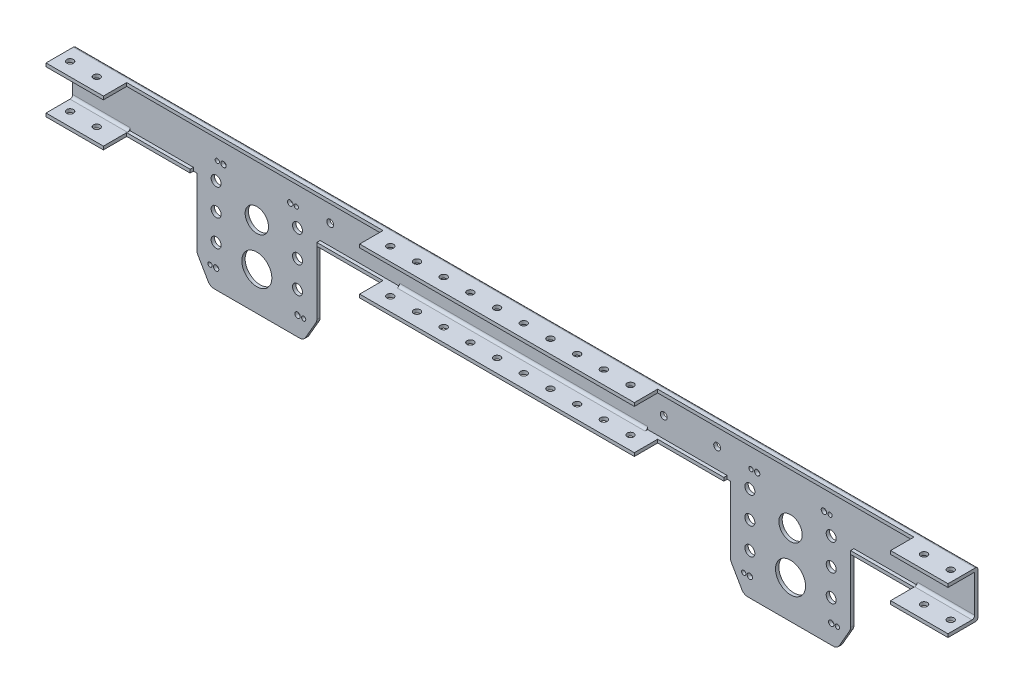
SolidWorks part; units mm, degrees
ref_plane "Front Plane" through (0, 0, 0) normal (0, 0, 1) x (1, 0, 0)
ref_plane "Top Plane" through (0, 0, 0) normal (0, 1, 0) x (1, 0, 0)
ref_plane "Right Plane" through (0, 0, 0) normal (1, 0, 0) x (0, 0, -1)
sketch "Sketch1" plane through (0, 0, 0) normal (0, 0, 1) x (1, 0, 0)
  line L0 (50.8, 0) -> (50.8, 25.4)
  line L1 (-50.8, 0) -> (-50.8, 76.2)
  line L2 (57.15, 31.75) -> (438.15, 31.75)
  line L3 (444.5, 25.4) -> (444.5, 0)
  line L4 (546.1, 0) -> (546.1, 76.2)
  line L5 (-50.8, 76.2) -> (546.1, 76.2)
  arc A0 (-50.8, 0) -> (50.8, 0) centre (0, 0) ccw
  arc A1 (50.8, 25.4) -> (57.15, 31.75) centre (57.15, 25.4) cw
  arc A2 (438.15, 31.75) -> (444.5, 25.4) centre (438.15, 25.4) cw
  arc A3 (444.5, 0) -> (546.1, 0) centre (495.3, 0) ccw
  circle A4 centre (0, 0) radius 6.35
  circle A5 centre (495.3, 0) radius 6.35
  dimension "D1" = 101.6
  dimension "D2" = 6.35
  dimension "D4" = 6.35
  dimension "D6" = 76.2
  dimension "D3" = 381
  dimension "D5" = 25.4
  dimension "D7" = 76.2
extrude "Boss-Extrude1" add sketch "Sketch1" along normal blind 3.175
sketch "Sketch2" plane through (0, 0, 3.175) normal (0, 0, 1) x (1, 0, 0)
  line L0 (-50.8, 76.2) -> (-50.8, 73.025)
  line L1 (-50.8, 76.2) -> (-50.8, 0) construction
  line L2 (546.1, 76.2) -> (-50.8, 76.2)
  line L3 (-50.8, 73.025) -> (546.1, 73.025)
  line L4 (546.1, 0) -> (546.1, 76.2) construction
  line L5 (546.1, 73.025) -> (546.1, 76.2)
  dimension "D1" = 3.175
extrude "Boss-Extrude2" add sketch "Sketch2" along normal blind 25.4
fillet "Fillet1" radius 2.54 2 edges at (247.65, 76.2, 0)
sketch "Sketch3" plane through (0, 76.2, 0) normal (0, 1, 0) x (1, 0, 0)
  line L0 (546.1, -28.575) -> (546.1, -2.54)
  circle A0 centre (527.05, -15.5575) radius 3.2639
  circle A1 centre (501.65, -15.5575) radius 3.2639
  circle A2 centre (476.25, -15.5575) radius 3.2639
  circle A3 centre (450.85, -15.5575) radius 3.2639
  circle A4 centre (425.45, -15.5575) radius 3.2639
  circle A5 centre (400.05, -15.5575) radius 3.2639
  circle A6 centre (374.65, -15.5575) radius 3.2639
  circle A7 centre (349.25, -15.5575) radius 3.2639
  circle A8 centre (323.85, -15.5575) radius 3.2639
  circle A9 centre (298.45, -15.5575) radius 3.2639
  circle A10 centre (273.05, -15.5575) radius 3.2639
  circle A11 centre (247.65, -15.5575) radius 3.2639
  circle A12 centre (222.25, -15.5575) radius 3.2639
  circle A13 centre (196.85, -15.5575) radius 3.2639
  circle A14 centre (171.45, -15.5575) radius 3.2639
  circle A15 centre (146.05, -15.5575) radius 3.2639
  circle A16 centre (120.65, -15.5575) radius 3.2639
  circle A17 centre (95.25, -15.5575) radius 3.2639
  circle A18 centre (69.85, -15.5575) radius 3.2639
  circle A19 centre (44.45, -15.5575) radius 3.2639
  circle A20 centre (19.05, -15.5575) radius 3.2639
  circle A21 centre (-6.35, -15.5575) radius 3.2639
  circle A22 centre (-31.75, -15.5575) radius 3.2639
  dimension "D1" = 19.05
  dimension "D2" = 23
extrude "Cut-Extrude1" cut sketch "Sketch3" against normal blind 25.4 contours A0 | A1 | A2 | A3 | A22 | A21 | A20 | A19 | A18 | A17 | A16 | A15 | A14 | A13 | A12 | A11 | A10 | A9 | A8 | A7 | A6 | A5 | A4 region at (527.05, 76.2, 15.5575) region at (501.65, 76.2, 15.5575) region at (476.25, 76.2, 15.5575) region at (450.85, 76.2, 15.5575) region at (425.45, 76.2, 15.5575) region at (400.05, 76.2, 15.5575) region at (374.65, 76.2, 15.5575) region at (349.25, 76.2, 15.5575) region at (323.85, 76.2, 15.5575) region at (298.45, 76.2, 15.5575) region at (273.05, 76.2, 15.5575) region at (247.65, 76.2, 15.5575) region at (222.25, 76.2, 15.5575) region at (196.85, 76.2, 15.5575) region at (171.45, 76.2, 15.5575) region at (146.05, 76.2, 15.5575) region at (120.65, 76.2, 15.5575) region at (95.25, 76.2, 15.5575) region at (69.85, 76.2, 15.5575) region at (44.45, 76.2, 15.5575) region at (19.05, 76.2, 15.5575) region at (-6.35, 76.2, 15.5575) region at (-31.75, 76.2, 15.5575)
sketch "Sketch5" plane through (0, 0, 0) normal (0, 0, -1) x (-1, 0, 0)
  line L0 (-444.5, 25.4) -> (-444.5, 0) construction
  circle A0 centre (-425.45, 53.975) radius 3.2639
  circle A1 centre (-374.65, 53.975) radius 3.2639
  circle A2 centre (-323.85, 53.975) radius 3.2639
  circle A3 centre (-273.05, 53.975) radius 3.2639
  circle A4 centre (-222.25, 53.975) radius 3.2639
  circle A5 centre (-171.45, 53.975) radius 3.2639
  circle A6 centre (-120.65, 53.975) radius 3.2639
  circle A7 centre (-69.85, 53.975) radius 3.2639
  dimension "D1" = 6.5278
  dimension "D2" = 19.05
  dimension "D3" = 8
extrude "Cut-Extrude2" cut sketch "Sketch5" against normal blind 25.4
sketch "Sketch6" plane through (0, 0, 3.175) normal (0, 0, 1) x (1, 0, 0)
  line L1 (-50.8, 76.2) -> (-82.55, 76.2)
  line L2 (-50.8, 76.2) -> (-50.8, 31.75)
  line L3 (-50.8, 31.75) -> (-82.55, 31.75)
  line L4 (-82.55, 76.2) -> (-82.55, 31.75)
  line L5 (546.1, 76.2) -> (577.85, 76.2)
  line L6 (546.1, 76.2) -> (546.1, 31.75)
  line L7 (546.1, 31.75) -> (577.85, 31.75)
  line L8 (577.85, 76.2) -> (577.85, 31.75)
  dimension "D1" = 31.75
  dimension "D2" = 31.75
extrude "Boss-Extrude3" add sketch "Sketch6" against normal blind 3.175
sketch "Sketch7" plane through (0, 0, 3.175) normal (0, 0, 1) x (1, 0, 0)
  line L1 (57.15, 31.75) -> (438.15, 31.75) construction
  line L2 (-50.8, 73.025) -> (-82.55, 73.025)
  line L3 (-50.8, 73.025) -> (-50.8, 76.2)
  line L4 (-50.8, 76.2) -> (-82.55, 76.2)
  line L5 (-82.55, 31.75) -> (-50.8, 31.75)
  line L6 (-82.55, 31.75) -> (-82.55, 34.925)
  line L7 (-82.55, 34.925) -> (-50.8, 34.925)
  line L8 (-50.8, 31.75) -> (-50.8, 34.925)
  line L9 (577.85, 31.75) -> (577.85, 76.2) construction
  line L10 (546.1, 76.2) -> (577.85, 76.2)
  line L11 (546.1, 76.2) -> (546.1, 73.025)
  line L12 (546.1, 73.025) -> (577.85, 73.025)
  line L13 (577.85, 76.2) -> (577.85, 73.025)
  line L14 (-82.55, 73.025) -> (-82.55, 76.2)
  line L15 (577.85, 31.75) -> (546.1, 31.75)
  line L16 (577.85, 31.75) -> (577.85, 34.925)
  line L17 (577.85, 34.925) -> (546.1, 34.925)
  line L18 (546.1, 31.75) -> (546.1, 34.925)
  line L19 (57.15, 31.75) -> (438.15, 31.75)
  line L20 (57.15, 31.75) -> (57.15, 34.925)
  line L21 (57.15, 34.925) -> (438.15, 34.925)
  line L22 (438.15, 31.75) -> (438.15, 34.925)
  arc A0 (57.15, 31.75) -> (50.8, 25.4) centre (57.15, 25.4) ccw construction
  dimension "D1" = 3.175
  dimension "D2" = 3.175
  dimension "D3" = 3.175
extrude "Boss-Extrude4" add sketch "Sketch7" along normal blind 25.4
fillet "Fillet2" radius 2.54 16 edges at (-50.8, 15.875, 0) (0, -50.8, 0) (50.8, 12.7, 0) (52.6599, 29.8901, 0) (546.1, 15.875, 0) (495.3, -50.8, 0) (444.5, 12.7, 0) (442.6401, 29.8901, 0) (-66.675, 34.925, 3.175) (-66.675, 31.75, 0) (247.65, 31.75, 0) (247.65, 34.925, 3.175) (561.975, 34.925, 3.175) (561.975, 31.75, 0) (561.975, 76.2, 0) (-66.675, 76.2, 0)
sketch "Sketch8" plane through (0, 76.2, 0) normal (0, 1, 0) x (1, 0, 0)
  circle A0 centre (-31.75, -15.5575) radius 3.2639 construction
  circle A1 centre (-31.75, -15.5575) radius 3.2639
  circle A2 centre (-57.15, -15.5575) radius 3.2639
  circle A3 centre (-31.75, -15.5575) radius 3.2639
  circle A4 centre (-6.35, -15.5575) radius 3.2639
  circle A5 centre (19.05, -15.5575) radius 3.2639
  circle A6 centre (44.45, -15.5575) radius 3.2639
  circle A7 centre (69.85, -15.5575) radius 3.2639
  circle A8 centre (95.25, -15.5575) radius 3.2639
  circle A9 centre (120.65, -15.5575) radius 3.2639
  circle A10 centre (146.05, -15.5575) radius 3.2639
  circle A11 centre (171.45, -15.5575) radius 3.2639
  circle A12 centre (196.85, -15.5575) radius 3.2639
  circle A13 centre (222.25, -15.5575) radius 3.2639
  circle A14 centre (247.65, -15.5575) radius 3.2639
  circle A15 centre (273.05, -15.5575) radius 3.2639
  circle A16 centre (298.45, -15.5575) radius 3.2639
  circle A17 centre (323.85, -15.5575) radius 3.2639
  circle A18 centre (349.25, -15.5575) radius 3.2639
  circle A19 centre (374.65, -15.5575) radius 3.2639
  circle A20 centre (400.05, -15.5575) radius 3.2639
  circle A21 centre (425.45, -15.5575) radius 3.2639
  circle A22 centre (450.85, -15.5575) radius 3.2639
  circle A23 centre (476.25, -15.5575) radius 3.2639
  circle A24 centre (501.65, -15.5575) radius 3.2639
  circle A25 centre (527.05, -15.5575) radius 3.2639
  circle A26 centre (-6.35, -15.5575) radius 3.2639
  circle A27 centre (19.05, -15.5575) radius 3.2639
  circle A28 centre (44.45, -15.5575) radius 3.2639
  circle A29 centre (69.85, -15.5575) radius 3.2639
  circle A30 centre (95.25, -15.5575) radius 3.2639
  circle A31 centre (120.65, -15.5575) radius 3.2639
  circle A32 centre (146.05, -15.5575) radius 3.2639
  circle A33 centre (171.45, -15.5575) radius 3.2639
  circle A34 centre (196.85, -15.5575) radius 3.2639
  circle A35 centre (222.25, -15.5575) radius 3.2639
  circle A36 centre (247.65, -15.5575) radius 3.2639
  circle A37 centre (273.05, -15.5575) radius 3.2639
  circle A38 centre (298.45, -15.5575) radius 3.2639
  circle A39 centre (323.85, -15.5575) radius 3.2639
  circle A40 centre (349.25, -15.5575) radius 3.2639
  circle A41 centre (374.65, -15.5575) radius 3.2639
  circle A42 centre (400.05, -15.5575) radius 3.2639
  circle A43 centre (425.45, -15.5575) radius 3.2639
  circle A44 centre (450.85, -15.5575) radius 3.2639
  circle A45 centre (476.25, -15.5575) radius 3.2639
  circle A46 centre (501.65, -15.5575) radius 3.2639
  circle A47 centre (527.05, -15.5575) radius 3.2639
  circle A48 centre (552.45, -15.5575) radius 3.2639
  circle M1 centre (425.45, -15.5575) radius 3.2639
  circle M2 centre (400.05, -15.5575) radius 3.2639
  circle M3 centre (374.65, -15.5575) radius 3.2639
  circle M4 centre (349.25, -15.5575) radius 3.2639
  circle M5 centre (323.85, -15.5575) radius 3.2639
  circle M6 centre (298.45, -15.5575) radius 3.2639
  circle M7 centre (273.05, -15.5575) radius 3.2639
  circle M8 centre (247.65, -15.5575) radius 3.2639
  circle M9 centre (222.25, -15.5575) radius 3.2639
  circle M10 centre (196.85, -15.5575) radius 3.2639
  circle M11 centre (171.45, -15.5575) radius 3.2639
  circle M12 centre (146.05, -15.5575) radius 3.2639
  circle M13 centre (120.65, -15.5575) radius 3.2639
  circle M14 centre (95.25, -15.5575) radius 3.2639
  circle M15 centre (69.85, -15.5575) radius 3.2639
  circle M16 centre (44.45, -15.5575) radius 3.2639
  circle M17 centre (19.05, -15.5575) radius 3.2639
  circle M18 centre (-6.35, -15.5575) radius 3.2639
  circle M19 centre (-31.75, -15.5575) radius 3.2639
  circle M20 centre (450.85, -15.5575) radius 3.2639
  circle M21 centre (476.25, -15.5575) radius 3.2639
  circle M22 centre (501.65, -15.5575) radius 3.2639
  circle M23 centre (527.05, -15.5575) radius 3.2639
  dimension "D1" = 2
  dimension "D2" = 24
extrude "Cut-Extrude3" cut sketch "Sketch8" against normal blind 177.8 contours A2 | M19 | M18 | M17 | M16 | M15 | M14 | M13 | M12 | M11 | M10 | M9 | M8 | M7 | M6 | M5 | M4 | M3 | M2 | M1 | M20 | M21 | A48 | M23 | M22 region at (-31.75, 76.2, 15.5575) region at (-57.15, 76.2, 15.5575) region at (-6.35, 76.2, 15.5575) region at (19.05, 76.2, 15.5575) region at (44.45, 76.2, 15.5575) region at (69.85, 76.2, 15.5575) region at (95.25, 76.2, 15.5575) region at (120.65, 76.2, 15.5575) region at (146.05, 76.2, 15.5575) region at (171.45, 76.2, 15.5575) region at (196.85, 76.2, 15.5575) region at (222.25, 76.2, 15.5575) region at (247.65, 76.2, 15.5575) region at (273.05, 76.2, 15.5575) region at (298.45, 76.2, 15.5575) region at (323.85, 76.2, 15.5575) region at (349.25, 76.2, 15.5575) region at (374.65, 76.2, 15.5575) region at (400.05, 76.2, 15.5575) region at (425.45, 76.2, 15.5575) region at (450.85, 76.2, 15.5575) region at (476.25, 76.2, 15.5575) region at (501.65, 76.2, 15.5575) region at (527.05, 76.2, 15.5575) region at (552.45, 76.2, 15.5575)
sketch "Sketch9" plane through (0, 76.2, 0) normal (0, 1, 0) x (1, 0, 0)
  line L0 (-82.55, -28.575) -> (298.45, -28.575)
  line L1 (577.85, -28.575) -> (-82.55, -28.575) construction
  line L3 (298.45, -28.575) -> (746.3929, -28.575)
  line L4 (298.45, -28.575) -> (298.45, 89.0041)
  line L5 (298.45, 89.0041) -> (746.3929, 89.0041)
  line L6 (746.3929, -28.575) -> (746.3929, 89.0041)
  circle M1 centre (552.45, -15.5575) radius 3.2639
  circle M3 centre (425.45, -15.5575) radius 3.2639
  circle M4 centre (400.05, -15.5575) radius 3.2639
  circle M5 centre (374.65, -15.5575) radius 3.2639
  circle M6 centre (349.25, -15.5575) radius 3.2639
  circle M7 centre (323.85, -15.5575) radius 3.2639
  circle M8 centre (298.45, -15.5575) radius 3.2639
  circle M22 centre (450.85, -15.5575) radius 3.2639
  circle M23 centre (476.25, -15.5575) radius 3.2639
  circle M24 centre (501.65, -15.5575) radius 3.2639
  circle M25 centre (527.05, -15.5575) radius 3.2639
  line M26 (577.85, -28.575) -> (577.85, -2.54)
  line M27 (577.85, -2.54) -> (546.1, -2.54)
  line M28 (546.1, -2.54) -> (-50.8, -2.54)
  line M31 (-82.55, -28.575) -> (577.85, -28.575)
extrude "Cut-Extrude5" cut sketch "Sketch9" against normal blind 432.308 contours L4 M31 M26 M27 M28 M8 M4 M6 M22 M24 M25 M23 M7 M5 M3 M1 | L3 L6 L5 L4 M28 M27 M26 region at (438.4843, 76.2, 15.5575) region at (535.9254, 76.2, -37.5492)
mirror "Mirror4" about plane through (298.45, -356.108, 0) normal (1, 0, 0) of bodies 110
sketch "Sketch10" plane through (-82.55, 0, 0) normal (-1, 0, 0) x (0, 0, 1)
  line L8 (0, 73.66) -> (0, 34.29)
  line L9 (2.54, 31.75) -> (28.575, 31.75)
  line L10 (28.575, 31.75) -> (28.575, 34.925)
  line L11 (28.575, 34.925) -> (5.715, 34.925)
  line L12 (3.175, 37.465) -> (3.175, 73.025)
  line L13 (3.175, 73.025) -> (28.575, 73.025)
  line L14 (28.575, 73.025) -> (28.575, 76.2)
  line L15 (28.575, 76.2) -> (2.54, 76.2)
  line L16 (0, 73.66) -> (0, 34.29)
  line L17 (2.54, 31.75) -> (28.575, 31.75)
  line L18 (28.575, 31.75) -> (28.575, 34.925)
  line L19 (28.575, 34.925) -> (5.715, 34.925)
  line L20 (3.175, 37.465) -> (3.175, 73.025)
  line L21 (3.175, 73.025) -> (28.575, 73.025)
  line L22 (28.575, 73.025) -> (28.575, 76.2)
  line L23 (28.575, 76.2) -> (2.54, 76.2)
  arc A3 (0, 34.29) -> (2.54, 31.75) centre (2.54, 34.29) ccw
  arc A4 (3.175, 37.465) -> (5.715, 34.925) centre (5.715, 37.465) ccw
  arc A5 (2.54, 76.2) -> (0, 73.66) centre (2.54, 73.66) ccw
  arc A6 (0, 34.29) -> (2.54, 31.75) centre (2.54, 34.29) ccw
  arc A7 (3.175, 37.465) -> (5.715, 34.925) centre (5.715, 37.465) ccw
  arc A8 (2.54, 76.2) -> (0, 73.66) centre (2.54, 73.66) ccw
  dimension "D1" = 0
extrude "Boss-Extrude6" add sketch "Sketch10" along normal blind 66.675
sketch "Sketch11" plane through (679.45, 0, 0) normal (1, 0, 0) x (0, 0, -1)
  line L8 (0, 34.29) -> (0, 73.66)
  line L9 (-2.54, 76.2) -> (-28.575, 76.2)
  line L10 (-28.575, 76.2) -> (-28.575, 73.025)
  line L11 (-28.575, 73.025) -> (-3.175, 73.025)
  line L12 (-3.175, 73.025) -> (-3.175, 37.465)
  line L13 (-5.715, 34.925) -> (-28.575, 34.925)
  line L14 (-28.575, 34.925) -> (-28.575, 31.75)
  line L15 (-28.575, 31.75) -> (-2.54, 31.75)
  line L16 (0, 34.29) -> (0, 73.66)
  line L17 (-2.54, 76.2) -> (-28.575, 76.2)
  line L18 (-28.575, 76.2) -> (-28.575, 73.025)
  line L19 (-28.575, 73.025) -> (-3.175, 73.025)
  line L20 (-3.175, 73.025) -> (-3.175, 37.465)
  line L21 (-5.715, 34.925) -> (-28.575, 34.925)
  line L22 (-28.575, 34.925) -> (-28.575, 31.75)
  line L23 (-28.575, 31.75) -> (-2.54, 31.75)
  arc A3 (0, 73.66) -> (-2.54, 76.2) centre (-2.54, 73.66) ccw
  arc A4 (-5.715, 34.925) -> (-3.175, 37.465) centre (-5.715, 37.465) ccw
  arc A5 (-2.54, 31.75) -> (0, 34.29) centre (-2.54, 34.29) ccw
  arc A6 (0, 73.66) -> (-2.54, 76.2) centre (-2.54, 73.66) ccw
  arc A7 (-5.715, 34.925) -> (-3.175, 37.465) centre (-5.715, 37.465) ccw
  arc A8 (-2.54, 31.75) -> (0, 34.29) centre (-2.54, 34.29) ccw
  dimension "D1" = 0
extrude "Boss-Extrude7" add sketch "Sketch11" along normal blind 66.675
sketch "Sketch12" plane through (0, 0, 3.175) normal (0, 0, 1) x (1, 0, 0)
  line L1 (114.3, 114.3) -> (-114.3, 114.3)
  line L2 (460.9211, 135.1062) -> (717.55, 135.1062)
  line L3 (460.9211, 135.1062) -> (460.9211, -117.6098)
  line L4 (482.6, 135.1062) -> (692.7253, 135.1062)
  line L5 (692.7253, 135.1062) -> (711.2, 135.1062)
  line L6 (460.9211, -117.6098) -> (717.55, -117.6098)
  line L7 (717.55, 135.1062) -> (717.55, -117.6098)
  line L8 (482.6, 135.1062) -> (460.9211, 135.1062)
  line L11 (460.9211, 135.1062) -> (460.9211, -59.2459)
  line L12 (711.2, 135.1062) -> (717.55, 135.1062)
  line L15 (717.55, 135.1062) -> (717.55, 3.7539)
  line L16 (114.3, 114.3) -> (135.9789, 114.3)
  line L17 (114.3, 0) -> (114.3, -15.4588)
  line L18 (114.3, -15.4588) -> (135.9789, -15.4588)
  line L19 (135.9789, 114.3) -> (135.9789, -15.4588)
  line L20 (-114.3, 114.3) -> (-120.65, 114.3)
  line L21 (-114.3, 0) -> (-114.3, -7.9863)
  line L22 (-114.3, -7.9863) -> (-120.65, -7.9863)
  line L23 (-120.65, 114.3) -> (-120.65, -7.9863)
  arc A0 (-114.3, 0) -> (114.3, 0) centre (0, 0) ccw
  circle M1 centre (0, 0) radius 6.35
  circle M5 centre (120.65, 53.975) radius 3.2639
  circle M6 centre (69.85, 53.975) radius 3.2639
  line M7 (57.15, 37.465) -> (539.75, 37.465)
  line M8 (539.75, 37.465) -> (539.75, 31.75)
  arc M9 (539.75, 31.75) -> (546.1, 25.4) centre (539.75, 25.4) cw
  line M10 (546.1, 25.4) -> (546.1, 0)
  arc M11 (546.1, 0) -> (647.7, 0) centre (596.9, 0) ccw
  line M12 (647.7, 0) -> (647.7, 31.75)
  line M13 (647.7, 31.75) -> (647.7, 37.465)
  line M14 (647.7, 37.465) -> (746.125, 37.465)
  line M16 (746.125, 73.025) -> (647.7, 73.025)
  line M17 (647.7, 73.025) -> (647.7, 70.485)
  line M18 (647.7, 70.485) -> (-50.8, 70.485)
  line M19 (-50.8, 70.485) -> (-50.8, 73.025)
  line M20 (-50.8, 73.025) -> (-149.225, 73.025)
  line M22 (-149.225, 37.465) -> (-50.8, 37.465)
  line M23 (-50.8, 37.465) -> (-50.8, 31.75)
  line M24 (-50.8, 31.75) -> (-50.8, 0)
  arc M25 (-50.8, 0) -> (50.8, 0) centre (0, 0) ccw
  line M26 (50.8, 0) -> (50.8, 25.4)
  arc M27 (50.8, 25.4) -> (57.15, 31.75) centre (57.15, 25.4) cw
  line M28 (57.15, 31.75) -> (57.15, 37.465)
  circle M29 centre (596.9, 0) radius 6.35
  circle M33 centre (476.25, 53.975) radius 3.2639
  circle M34 centre (527.05, 53.975) radius 3.2639
  dimension "D1" = 13.335
  dimension "D2" = 6.35
  dimension "D3" = 13.335
  dimension "D4" = 6.35
extrude "Cut-Extrude8" cut sketch "Sketch12" along normal blind 66.675 contours L7 L3 L6 M14 M13 M12 M11 M10 M9 M8 M7 | L7 L3 M16 M17 M18 M7 M8 M9 M10 M11 M12 M13 M14 M34 M33 M29 | L7 L2 L3 M18 M17 M16 | L21 A0 L17 L18 L19 L23 L22 M7 M28 M27 M26 M25 M24 M23 M22 | L23 L19 M20 M22 M23 M24 M25 M26 M27 M28 M7 M18 M19 M6 M5 M1 | L20 L23 L19 L16 L1 M20 M19 M18 region at (9.1616, 92.7234, 3.175) region at (2.7974, 27.6189, 3.175) region at (132.9974, 11.0031, 3.175) region at (594.1026, 27.6189, 3.175) region at (588.2256, 103.1313, 3.175) region at (500.3355, 34.4666, 3.175)
sketch "Sketch13" plane through (0, 76.2, 0) normal (0, 1, 0) x (1, 0, 0)
  circle A0 centre (146.05, -15.5575) radius 3.2639 construction
  circle A1 centre (146.05, -15.5575) radius 3.2639
sketch "Sketch14" plane through (746.125, 0, 0) normal (1, 0, 0) x (0, 0, -1)
  line L8 (0, 34.29) -> (0, 73.66)
  line L9 (-2.54, 76.2) -> (-28.575, 76.2)
  line L10 (-28.575, 76.2) -> (-28.575, 73.025)
  line L11 (-28.575, 73.025) -> (-3.175, 73.025)
  line L12 (-3.175, 73.025) -> (-3.175, 37.465)
  line L13 (-5.715, 34.925) -> (-28.575, 34.925)
  line L14 (-28.575, 34.925) -> (-28.575, 31.75)
  line L15 (-28.575, 31.75) -> (-2.54, 31.75)
  line L16 (0, 34.29) -> (0, 73.66)
  line L17 (-2.54, 76.2) -> (-28.575, 76.2)
  line L18 (-28.575, 76.2) -> (-28.575, 73.025)
  line L19 (-28.575, 73.025) -> (-3.175, 73.025)
  line L20 (-3.175, 73.025) -> (-3.175, 37.465)
  line L21 (-5.715, 34.925) -> (-28.575, 34.925)
  line L22 (-28.575, 34.925) -> (-28.575, 31.75)
  line L23 (-28.575, 31.75) -> (-2.54, 31.75)
  arc A3 (-2.54, 31.75) -> (0, 34.29) centre (-2.54, 34.29) ccw
  arc A4 (0, 73.66) -> (-2.54, 76.2) centre (-2.54, 73.66) ccw
  arc A5 (-5.715, 34.925) -> (-3.175, 37.465) centre (-5.715, 37.465) ccw
  arc A6 (-2.54, 31.75) -> (0, 34.29) centre (-2.54, 34.29) ccw
  arc A7 (0, 73.66) -> (-2.54, 76.2) centre (-2.54, 73.66) ccw
  arc A8 (-5.715, 34.925) -> (-3.175, 37.465) centre (-5.715, 37.465) ccw
  dimension "D1" = 0
extrude "Boss-Extrude8" add sketch "Sketch14" along normal blind 19.05
sketch "Sketch15" plane through (-149.225, 0, 0) normal (-1, 0, 0) x (0, 0, 1)
  line L8 (0, 73.66) -> (0, 34.29)
  line L9 (2.54, 31.75) -> (28.575, 31.75)
  line L10 (28.575, 31.75) -> (28.575, 34.925)
  line L11 (28.575, 34.925) -> (5.715, 34.925)
  line L12 (3.175, 37.465) -> (3.175, 73.025)
  line L13 (3.175, 73.025) -> (28.575, 73.025)
  line L14 (28.575, 73.025) -> (28.575, 76.2)
  line L15 (28.575, 76.2) -> (2.54, 76.2)
  line L16 (0, 73.66) -> (0, 34.29)
  line L17 (2.54, 31.75) -> (28.575, 31.75)
  line L18 (28.575, 31.75) -> (28.575, 34.925)
  line L19 (28.575, 34.925) -> (5.715, 34.925)
  line L20 (3.175, 37.465) -> (3.175, 73.025)
  line L21 (3.175, 73.025) -> (28.575, 73.025)
  line L22 (28.575, 73.025) -> (28.575, 76.2)
  line L23 (28.575, 76.2) -> (2.54, 76.2)
  arc A3 (2.54, 76.2) -> (0, 73.66) centre (2.54, 73.66) ccw
  arc A4 (0, 34.29) -> (2.54, 31.75) centre (2.54, 34.29) ccw
  arc A5 (3.175, 37.465) -> (5.715, 34.925) centre (5.715, 37.465) ccw
  arc A6 (2.54, 76.2) -> (0, 73.66) centre (2.54, 73.66) ccw
  arc A7 (0, 34.29) -> (2.54, 31.75) centre (2.54, 34.29) ccw
  arc A8 (3.175, 37.465) -> (5.715, 34.925) centre (5.715, 37.465) ccw
  dimension "D1" = 0
extrude "Boss-Extrude9" add sketch "Sketch15" along normal blind 19.05
sketch "Sketch16" plane through (0, 76.2, 0) normal (0, 1, 0) x (1, 0, 0)
  circle A0 centre (146.05, -15.5575) radius 3.2639 construction
  circle A1 centre (146.05, -15.5575) radius 3.2639
  circle A2 centre (171.45, -15.5575) radius 3.2639
  circle A3 centre (196.85, -15.5575) radius 3.2639
  circle A4 centre (222.25, -15.5575) radius 3.2639
  circle A5 centre (247.65, -15.5575) radius 3.2639
  circle A6 centre (273.05, -15.5575) radius 3.2639
  circle A7 centre (298.45, -15.5575) radius 3.2639
  circle A8 centre (323.85, -15.5575) radius 3.2639
  circle A9 centre (349.25, -15.5575) radius 3.2639
  circle A10 centre (374.65, -15.5575) radius 3.2639
  circle A11 centre (400.05, -15.5575) radius 3.2639
  circle A12 centre (425.45, -15.5575) radius 3.2639
  circle A13 centre (450.85, -15.5575) radius 3.2639
  circle A14 centre (476.25, -15.5575) radius 3.2639
  circle A15 centre (501.65, -15.5575) radius 3.2639
  circle A16 centre (527.05, -15.5575) radius 3.2639
  circle A17 centre (552.45, -15.5575) radius 3.2639
  circle A18 centre (577.85, -15.5575) radius 3.2639
  circle A19 centre (603.25, -15.5575) radius 3.2639
  circle A20 centre (628.65, -15.5575) radius 3.2639
  circle A21 centre (654.05, -15.5575) radius 3.2639
  circle A22 centre (679.45, -15.5575) radius 3.2639
  circle A23 centre (704.85, -15.5575) radius 3.2639
  circle A24 centre (730.25, -15.5575) radius 3.2639
  circle A25 centre (755.65, -15.5575) radius 3.2639
  circle A26 centre (146.05, -15.5575) radius 3.2639
  circle A27 centre (171.45, -15.5575) radius 3.2639
  circle A28 centre (196.85, -15.5575) radius 3.2639
  circle A29 centre (222.25, -15.5575) radius 3.2639
  circle A30 centre (247.65, -15.5575) radius 3.2639
  circle A31 centre (273.05, -15.5575) radius 3.2639
  circle A32 centre (298.45, -15.5575) radius 3.2639
  circle A33 centre (323.85, -15.5575) radius 3.2639
  circle A34 centre (349.25, -15.5575) radius 3.2639
  circle A35 centre (374.65, -15.5575) radius 3.2639
  circle A36 centre (400.05, -15.5575) radius 3.2639
  circle A37 centre (425.45, -15.5575) radius 3.2639
  circle A38 centre (450.85, -15.5575) radius 3.2639
  circle A39 centre (476.25, -15.5575) radius 3.2639
  circle A40 centre (501.65, -15.5575) radius 3.2639
  circle A41 centre (527.05, -15.5575) radius 3.2639
  circle A42 centre (552.45, -15.5575) radius 3.2639
  circle A43 centre (577.85, -15.5575) radius 3.2639
  circle A44 centre (603.25, -15.5575) radius 3.2639
  circle A45 centre (628.65, -15.5575) radius 3.2639
  circle A46 centre (654.05, -15.5575) radius 3.2639
  circle A47 centre (679.45, -15.5575) radius 3.2639
  circle A48 centre (704.85, -15.5575) radius 3.2639
  circle A49 centre (730.25, -15.5575) radius 3.2639
  circle A50 centre (120.65, -15.5575) radius 3.2639
  circle A51 centre (146.05, -15.5575) radius 3.2639
  circle A52 centre (171.45, -15.5575) radius 3.2639
  circle A53 centre (196.85, -15.5575) radius 3.2639
  circle A54 centre (222.25, -15.5575) radius 3.2639
  circle A55 centre (247.65, -15.5575) radius 3.2639
  circle A56 centre (273.05, -15.5575) radius 3.2639
  circle A57 centre (298.45, -15.5575) radius 3.2639
  circle A58 centre (323.85, -15.5575) radius 3.2639
  circle A59 centre (349.25, -15.5575) radius 3.2639
  circle A60 centre (374.65, -15.5575) radius 3.2639
  circle A61 centre (400.05, -15.5575) radius 3.2639
  circle A62 centre (425.45, -15.5575) radius 3.2639
  circle A63 centre (450.85, -15.5575) radius 3.2639
  circle A64 centre (476.25, -15.5575) radius 3.2639
  circle A65 centre (501.65, -15.5575) radius 3.2639
  circle A66 centre (527.05, -15.5575) radius 3.2639
  circle A67 centre (552.45, -15.5575) radius 3.2639
  circle A68 centre (577.85, -15.5575) radius 3.2639
  circle A69 centre (603.25, -15.5575) radius 3.2639
  circle A70 centre (628.65, -15.5575) radius 3.2639
  circle A71 centre (654.05, -15.5575) radius 3.2639
  circle A72 centre (679.45, -15.5575) radius 3.2639
  circle A73 centre (704.85, -15.5575) radius 3.2639
  circle A74 centre (95.25, -15.5575) radius 3.2639
  circle A75 centre (120.65, -15.5575) radius 3.2639
  circle A76 centre (146.05, -15.5575) radius 3.2639
  circle A77 centre (171.45, -15.5575) radius 3.2639
  circle A78 centre (196.85, -15.5575) radius 3.2639
  circle A79 centre (222.25, -15.5575) radius 3.2639
  circle A80 centre (247.65, -15.5575) radius 3.2639
  circle A81 centre (273.05, -15.5575) radius 3.2639
  circle A82 centre (298.45, -15.5575) radius 3.2639
  circle A83 centre (323.85, -15.5575) radius 3.2639
  circle A84 centre (349.25, -15.5575) radius 3.2639
  circle A85 centre (374.65, -15.5575) radius 3.2639
  circle A86 centre (400.05, -15.5575) radius 3.2639
  circle A87 centre (425.45, -15.5575) radius 3.2639
  circle A88 centre (450.85, -15.5575) radius 3.2639
  circle A89 centre (476.25, -15.5575) radius 3.2639
  circle A90 centre (501.65, -15.5575) radius 3.2639
  circle A91 centre (527.05, -15.5575) radius 3.2639
  circle A92 centre (552.45, -15.5575) radius 3.2639
  circle A93 centre (577.85, -15.5575) radius 3.2639
  circle A94 centre (603.25, -15.5575) radius 3.2639
  circle A95 centre (628.65, -15.5575) radius 3.2639
  circle A96 centre (654.05, -15.5575) radius 3.2639
  circle A97 centre (679.45, -15.5575) radius 3.2639
  circle A98 centre (69.85, -15.5575) radius 3.2639
  circle A99 centre (95.25, -15.5575) radius 3.2639
  circle A100 centre (120.65, -15.5575) radius 3.2639
  circle A101 centre (146.05, -15.5575) radius 3.2639
  circle A102 centre (171.45, -15.5575) radius 3.2639
  circle A103 centre (196.85, -15.5575) radius 3.2639
  circle A104 centre (222.25, -15.5575) radius 3.2639
  circle A105 centre (247.65, -15.5575) radius 3.2639
  circle A106 centre (273.05, -15.5575) radius 3.2639
  circle A107 centre (298.45, -15.5575) radius 3.2639
  circle A108 centre (323.85, -15.5575) radius 3.2639
  circle A109 centre (349.25, -15.5575) radius 3.2639
  circle A110 centre (374.65, -15.5575) radius 3.2639
  circle A111 centre (400.05, -15.5575) radius 3.2639
  circle A112 centre (425.45, -15.5575) radius 3.2639
  circle A113 centre (450.85, -15.5575) radius 3.2639
  circle A114 centre (476.25, -15.5575) radius 3.2639
  circle A115 centre (501.65, -15.5575) radius 3.2639
  circle A116 centre (527.05, -15.5575) radius 3.2639
  circle A117 centre (552.45, -15.5575) radius 3.2639
  circle A118 centre (577.85, -15.5575) radius 3.2639
  circle A119 centre (603.25, -15.5575) radius 3.2639
  circle A120 centre (628.65, -15.5575) radius 3.2639
  circle A121 centre (654.05, -15.5575) radius 3.2639
  circle A122 centre (44.45, -15.5575) radius 3.2639
  circle A123 centre (69.85, -15.5575) radius 3.2639
  circle A124 centre (95.25, -15.5575) radius 3.2639
  circle A125 centre (120.65, -15.5575) radius 3.2639
  circle A126 centre (146.05, -15.5575) radius 3.2639
  circle A127 centre (171.45, -15.5575) radius 3.2639
  circle A128 centre (196.85, -15.5575) radius 3.2639
  circle A129 centre (222.25, -15.5575) radius 3.2639
  circle A130 centre (247.65, -15.5575) radius 3.2639
  circle A131 centre (273.05, -15.5575) radius 3.2639
  circle A132 centre (298.45, -15.5575) radius 3.2639
  circle A133 centre (323.85, -15.5575) radius 3.2639
  circle A134 centre (349.25, -15.5575) radius 3.2639
  circle A135 centre (374.65, -15.5575) radius 3.2639
  circle A136 centre (400.05, -15.5575) radius 3.2639
  circle A137 centre (425.45, -15.5575) radius 3.2639
  circle A138 centre (450.85, -15.5575) radius 3.2639
  circle A139 centre (476.25, -15.5575) radius 3.2639
  circle A140 centre (501.65, -15.5575) radius 3.2639
  circle A141 centre (527.05, -15.5575) radius 3.2639
  circle A142 centre (552.45, -15.5575) radius 3.2639
  circle A143 centre (577.85, -15.5575) radius 3.2639
  circle A144 centre (603.25, -15.5575) radius 3.2639
  circle A145 centre (628.65, -15.5575) radius 3.2639
  circle A146 centre (19.05, -15.5575) radius 3.2639
  circle A147 centre (44.45, -15.5575) radius 3.2639
  circle A148 centre (69.85, -15.5575) radius 3.2639
  circle A149 centre (95.25, -15.5575) radius 3.2639
  circle A150 centre (120.65, -15.5575) radius 3.2639
  circle A151 centre (146.05, -15.5575) radius 3.2639
  circle A152 centre (171.45, -15.5575) radius 3.2639
  circle A153 centre (196.85, -15.5575) radius 3.2639
  circle A154 centre (222.25, -15.5575) radius 3.2639
  circle A155 centre (247.65, -15.5575) radius 3.2639
  circle A156 centre (273.05, -15.5575) radius 3.2639
  circle A157 centre (298.45, -15.5575) radius 3.2639
  circle A158 centre (323.85, -15.5575) radius 3.2639
  circle A159 centre (349.25, -15.5575) radius 3.2639
  circle A160 centre (374.65, -15.5575) radius 3.2639
  circle A161 centre (400.05, -15.5575) radius 3.2639
  circle A162 centre (425.45, -15.5575) radius 3.2639
  circle A163 centre (450.85, -15.5575) radius 3.2639
  circle A164 centre (476.25, -15.5575) radius 3.2639
  circle A165 centre (501.65, -15.5575) radius 3.2639
  circle A166 centre (527.05, -15.5575) radius 3.2639
  circle A167 centre (552.45, -15.5575) radius 3.2639
  circle A168 centre (577.85, -15.5575) radius 3.2639
  circle A169 centre (603.25, -15.5575) radius 3.2639
  circle A170 centre (-6.35, -15.5575) radius 3.2639
  circle A171 centre (19.05, -15.5575) radius 3.2639
  circle A172 centre (44.45, -15.5575) radius 3.2639
  circle A173 centre (69.85, -15.5575) radius 3.2639
  circle A174 centre (95.25, -15.5575) radius 3.2639
  circle A175 centre (120.65, -15.5575) radius 3.2639
  circle A176 centre (146.05, -15.5575) radius 3.2639
  circle A177 centre (171.45, -15.5575) radius 3.2639
  circle A178 centre (196.85, -15.5575) radius 3.2639
  circle A179 centre (222.25, -15.5575) radius 3.2639
  circle A180 centre (247.65, -15.5575) radius 3.2639
  circle A181 centre (273.05, -15.5575) radius 3.2639
  circle A182 centre (298.45, -15.5575) radius 3.2639
  circle A183 centre (323.85, -15.5575) radius 3.2639
  circle A184 centre (349.25, -15.5575) radius 3.2639
  circle A185 centre (374.65, -15.5575) radius 3.2639
  circle A186 centre (400.05, -15.5575) radius 3.2639
  circle A187 centre (425.45, -15.5575) radius 3.2639
  circle A188 centre (450.85, -15.5575) radius 3.2639
  circle A189 centre (476.25, -15.5575) radius 3.2639
  circle A190 centre (501.65, -15.5575) radius 3.2639
  circle A191 centre (527.05, -15.5575) radius 3.2639
  circle A192 centre (552.45, -15.5575) radius 3.2639
  circle A193 centre (577.85, -15.5575) radius 3.2639
  circle A194 centre (-31.75, -15.5575) radius 3.2639
  circle A195 centre (-6.35, -15.5575) radius 3.2639
  circle A196 centre (19.05, -15.5575) radius 3.2639
  circle A197 centre (44.45, -15.5575) radius 3.2639
  circle A198 centre (69.85, -15.5575) radius 3.2639
  circle A199 centre (95.25, -15.5575) radius 3.2639
  circle A200 centre (120.65, -15.5575) radius 3.2639
  circle A201 centre (146.05, -15.5575) radius 3.2639
  circle A202 centre (171.45, -15.5575) radius 3.2639
  circle A203 centre (196.85, -15.5575) radius 3.2639
  circle A204 centre (222.25, -15.5575) radius 3.2639
  circle A205 centre (247.65, -15.5575) radius 3.2639
  circle A206 centre (273.05, -15.5575) radius 3.2639
  circle A207 centre (298.45, -15.5575) radius 3.2639
  circle A208 centre (323.85, -15.5575) radius 3.2639
  circle A209 centre (349.25, -15.5575) radius 3.2639
  circle A210 centre (374.65, -15.5575) radius 3.2639
  circle A211 centre (400.05, -15.5575) radius 3.2639
  circle A212 centre (425.45, -15.5575) radius 3.2639
  circle A213 centre (450.85, -15.5575) radius 3.2639
  circle A214 centre (476.25, -15.5575) radius 3.2639
  circle A215 centre (501.65, -15.5575) radius 3.2639
  circle A216 centre (527.05, -15.5575) radius 3.2639
  circle A217 centre (552.45, -15.5575) radius 3.2639
  circle A218 centre (-57.15, -15.5575) radius 3.2639
  circle A219 centre (-31.75, -15.5575) radius 3.2639
  circle A220 centre (-6.35, -15.5575) radius 3.2639
  circle A221 centre (19.05, -15.5575) radius 3.2639
  circle A222 centre (44.45, -15.5575) radius 3.2639
  circle A223 centre (69.85, -15.5575) radius 3.2639
  circle A224 centre (95.25, -15.5575) radius 3.2639
  circle A225 centre (120.65, -15.5575) radius 3.2639
  circle A226 centre (146.05, -15.5575) radius 3.2639
  circle A227 centre (171.45, -15.5575) radius 3.2639
  circle A228 centre (196.85, -15.5575) radius 3.2639
  circle A229 centre (222.25, -15.5575) radius 3.2639
  circle A230 centre (247.65, -15.5575) radius 3.2639
  circle A231 centre (273.05, -15.5575) radius 3.2639
  circle A232 centre (298.45, -15.5575) radius 3.2639
  circle A233 centre (323.85, -15.5575) radius 3.2639
  circle A234 centre (349.25, -15.5575) radius 3.2639
  circle A235 centre (374.65, -15.5575) radius 3.2639
  circle A236 centre (400.05, -15.5575) radius 3.2639
  circle A237 centre (425.45, -15.5575) radius 3.2639
  circle A238 centre (450.85, -15.5575) radius 3.2639
  circle A239 centre (476.25, -15.5575) radius 3.2639
  circle A240 centre (501.65, -15.5575) radius 3.2639
  circle A241 centre (527.05, -15.5575) radius 3.2639
  circle A242 centre (-82.55, -15.5575) radius 3.2639
  circle A243 centre (-57.15, -15.5575) radius 3.2639
  circle A244 centre (-31.75, -15.5575) radius 3.2639
  circle A245 centre (-6.35, -15.5575) radius 3.2639
  circle A246 centre (19.05, -15.5575) radius 3.2639
  circle A247 centre (44.45, -15.5575) radius 3.2639
  circle A248 centre (69.85, -15.5575) radius 3.2639
  circle A249 centre (95.25, -15.5575) radius 3.2639
  circle A250 centre (120.65, -15.5575) radius 3.2639
  circle A251 centre (146.05, -15.5575) radius 3.2639
  circle A252 centre (171.45, -15.5575) radius 3.2639
  circle A253 centre (196.85, -15.5575) radius 3.2639
  circle A254 centre (222.25, -15.5575) radius 3.2639
  circle A255 centre (247.65, -15.5575) radius 3.2639
  circle A256 centre (273.05, -15.5575) radius 3.2639
  circle A257 centre (298.45, -15.5575) radius 3.2639
  circle A258 centre (323.85, -15.5575) radius 3.2639
  circle A259 centre (349.25, -15.5575) radius 3.2639
  circle A260 centre (374.65, -15.5575) radius 3.2639
  circle A261 centre (400.05, -15.5575) radius 3.2639
  circle A262 centre (425.45, -15.5575) radius 3.2639
  circle A263 centre (450.85, -15.5575) radius 3.2639
  circle A264 centre (476.25, -15.5575) radius 3.2639
  circle A265 centre (501.65, -15.5575) radius 3.2639
  circle A266 centre (-107.95, -15.5575) radius 3.2639
  circle A267 centre (-82.55, -15.5575) radius 3.2639
  circle A268 centre (-57.15, -15.5575) radius 3.2639
  circle A269 centre (-31.75, -15.5575) radius 3.2639
  circle A270 centre (-6.35, -15.5575) radius 3.2639
  circle A271 centre (19.05, -15.5575) radius 3.2639
  circle A272 centre (44.45, -15.5575) radius 3.2639
  circle A273 centre (69.85, -15.5575) radius 3.2639
  circle A274 centre (95.25, -15.5575) radius 3.2639
  circle A275 centre (120.65, -15.5575) radius 3.2639
  circle A276 centre (146.05, -15.5575) radius 3.2639
  circle A277 centre (171.45, -15.5575) radius 3.2639
  circle A278 centre (196.85, -15.5575) radius 3.2639
  circle A279 centre (222.25, -15.5575) radius 3.2639
  circle A280 centre (247.65, -15.5575) radius 3.2639
  circle A281 centre (273.05, -15.5575) radius 3.2639
  circle A282 centre (298.45, -15.5575) radius 3.2639
  circle A283 centre (323.85, -15.5575) radius 3.2639
  circle A284 centre (349.25, -15.5575) radius 3.2639
  circle A285 centre (374.65, -15.5575) radius 3.2639
  circle A286 centre (400.05, -15.5575) radius 3.2639
  circle A287 centre (425.45, -15.5575) radius 3.2639
  circle A288 centre (450.85, -15.5575) radius 3.2639
  circle A289 centre (476.25, -15.5575) radius 3.2639
  circle A290 centre (-133.35, -15.5575) radius 3.2639
  circle A291 centre (-107.95, -15.5575) radius 3.2639
  circle A292 centre (-82.55, -15.5575) radius 3.2639
  circle A293 centre (-57.15, -15.5575) radius 3.2639
  circle A294 centre (-31.75, -15.5575) radius 3.2639
  circle A295 centre (-6.35, -15.5575) radius 3.2639
  circle A296 centre (19.05, -15.5575) radius 3.2639
  circle A297 centre (44.45, -15.5575) radius 3.2639
  circle A298 centre (69.85, -15.5575) radius 3.2639
  circle A299 centre (95.25, -15.5575) radius 3.2639
  circle A300 centre (120.65, -15.5575) radius 3.2639
  circle A301 centre (146.05, -15.5575) radius 3.2639
  circle A302 centre (171.45, -15.5575) radius 3.2639
  circle A303 centre (196.85, -15.5575) radius 3.2639
  circle A304 centre (222.25, -15.5575) radius 3.2639
  circle A305 centre (247.65, -15.5575) radius 3.2639
  circle A306 centre (273.05, -15.5575) radius 3.2639
  circle A307 centre (298.45, -15.5575) radius 3.2639
  circle A308 centre (323.85, -15.5575) radius 3.2639
  circle A309 centre (349.25, -15.5575) radius 3.2639
  circle A310 centre (374.65, -15.5575) radius 3.2639
  circle A311 centre (400.05, -15.5575) radius 3.2639
  circle A312 centre (425.45, -15.5575) radius 3.2639
  circle A313 centre (450.85, -15.5575) radius 3.2639
  circle A314 centre (120.65, -15.5575) radius 3.2639
  circle A315 centre (95.25, -15.5575) radius 3.2639
  circle A316 centre (69.85, -15.5575) radius 3.2639
  circle A317 centre (44.45, -15.5575) radius 3.2639
  circle A318 centre (19.05, -15.5575) radius 3.2639
  circle A319 centre (-6.35, -15.5575) radius 3.2639
  circle A320 centre (-31.75, -15.5575) radius 3.2639
  circle A321 centre (-57.15, -15.5575) radius 3.2639
  circle A322 centre (-82.55, -15.5575) radius 3.2639
  circle A323 centre (-107.95, -15.5575) radius 3.2639
  circle A324 centre (-133.35, -15.5575) radius 3.2639
  circle A325 centre (-158.75, -15.5575) radius 3.2639
  dimension "D1" = 25
  dimension "D2" = 13
extrude "Cut-Extrude9" cut sketch "Sketch16" against normal blind 133.096
sketch "Sketch17" plane through (0, 0, 0) normal (0, 0, -1) x (-1, 0, 0)
  line L0 (-647.7, 76.2) -> (50.8, 76.2) construction
  circle A0 centre (0, 63.5) radius 3.175
  circle A1 centre (-596.9, 63.5) radius 3.175
  dimension "D1" = 12.7
extrude "Cut-Extrude11" cut sketch "Sketch17" against normal blind 5.08
sketch "Sketch18" plane through (0, 0, 3.175) normal (0, 0, 1) x (1, 0, 0)
  line L1 (-120.65, 73.025) -> (135.9789, 73.025)
  line L2 (-120.65, 73.025) -> (-120.65, 76.2)
  line L3 (-120.65, 76.2) -> (135.9789, 76.2)
  line L4 (135.9789, 73.025) -> (135.9789, 76.2)
  line L5 (460.9211, 76.2) -> (717.55, 76.2)
  line L6 (460.9211, 76.2) -> (460.9211, 73.025)
  line L7 (460.9211, 73.025) -> (717.55, 73.025)
  line L8 (717.55, 76.2) -> (717.55, 73.025)
  line L9 (717.55, 31.75) -> (-120.65, 31.75)
  line L10 (717.55, 31.75) -> (717.55, 34.925)
  line L11 (717.55, 34.925) -> (-120.65, 34.925)
  line L12 (-120.65, 31.75) -> (-120.65, 34.925)
extrude "Boss-Extrude10" add sketch "Sketch18" along normal blind 3.175
sketch "Sketch19" plane through (0, 0, 3.175) normal (0, 0, 1) x (1, 0, 0)
  line L0 (717.55, 34.925) -> (460.9211, 34.925) construction
  line L1 (-50.8, 31.75) -> (57.1504, 31.75)
  line L2 (-50.8, 31.75) -> (-50.8, 38.1387)
  line L3 (-50.8, 38.1387) -> (57.1504, 38.1387)
  line L4 (57.1504, 31.75) -> (57.1504, 38.1387)
  line L5 (647.7, 34.925) -> (539.75, 34.925)
  line L6 (647.7, 34.925) -> (647.7, 31.75)
  line L7 (647.7, 31.75) -> (539.75, 31.75)
  line L8 (539.75, 34.925) -> (539.75, 31.75)
extrude "Cut-Extrude12" cut sketch "Sketch19" along normal blind 3.175
sketch "Sketch20" plane through (0, 0, 0) normal (0, 0, -1) x (-1, 0, 0)
  line L0 (-342.9, 184.1305) -> (-342.9, -54.1947)
  line L2 (-342.9, 184.1305) -> (212.3723, 184.1305)
  line L3 (-342.9, 184.1305) -> (-342.9, -60.2979)
  line L4 (-342.9, -60.2979) -> (212.3723, -60.2979)
  line L5 (212.3723, 184.1305) -> (212.3723, -60.2979)
  circle A0 centre (-596.9, 0) radius 6.35 construction
  circle M3 centre (0, 63.5) radius 3.175
  circle M4 centre (0, 0) radius 6.35
  circle M5 centre (-273.05, 53.975) radius 3.2639
  circle M6 centre (-222.25, 53.975) radius 3.2639
  circle M7 centre (-171.45, 53.975) radius 3.2639
  circle M8 centre (-120.65, 53.975) radius 3.2639
  circle M9 centre (-69.85, 53.975) radius 3.2639
  line M10 (50.8, 73.66) -> (-647.7, 73.66)
  line M18 (-539.75, 34.29) -> (-57.15, 34.29)
  arc M19 (-57.15, 34.29) -> (-48.26, 25.4) centre (-57.15, 25.4) cw
  line M20 (-48.26, 25.4) -> (-48.26, 0)
  arc M21 (-48.26, 0) -> (48.26, 0) centre (0, 0) ccw
  line M22 (48.26, 0) -> (48.26, 34.29)
  line M23 (48.26, 34.29) -> (168.275, 34.29)
  line M24 (168.275, 34.29) -> (168.275, 73.66)
  line M25 (168.275, 73.66) -> (50.8, 73.66)
  circle M27 centre (-323.85, 53.975) radius 3.2639
  dimension "D1" = 254
extrude "Cut-Extrude13" cut sketch "Sketch20" against normal blind 277.622 contours L0 M10 M18 M19 M20 M21 M22 M23 M24 M25 M4 M6 M8 M27 M9 M7 M5 M3 | L5 L2 L0 L3 L4 M10 M25 M24 M23 M22 M21 M20 M19 M18 region at (65.2639, 178.0636, 0) region at (64.2403, 39.4662, 0)
sketch "Sketch21" plane through (0, 0, 3.175) normal (0, 0, 1) x (1, 0, 0)
  line L0 (546.1, 0) -> (546.1, 25.4) construction
  line L1 (647.7, 31.75) -> (647.7, 0) construction
  line L2 (546.1, 0) -> (546.1, 25.4)
  line L3 (647.7, 31.75) -> (647.7, 0)
  line L4 (539.75, 31.75) -> (539.75, 34.925)
  line L5 (539.75, 34.925) -> (647.7, 34.925)
  line L6 (647.7, 34.925) -> (647.7, 31.75)
  arc A0 (546.1, 25.4) -> (539.75, 31.75) centre (539.75, 25.4) ccw construction
  arc A1 (546.1, 0) -> (647.7, 0) centre (596.9, 0) ccw construction
  arc A2 (546.1, 25.4) -> (539.75, 31.75) centre (539.75, 25.4) ccw
  arc A3 (546.1, 0) -> (647.7, 0) centre (596.9, 0) ccw
  circle A4 centre (596.9, 0) radius 6.35 construction
  circle A5 centre (596.9, 0) radius 6.35
extrude "Boss-Extrude11" add sketch "Sketch21" against normal blind 3.175
mirror "Mirror5" about plane through (342.9, 0, 277.622) normal (1, 0, 0) of bodies 125
sketch "Sketch22" plane through (0, 76.2, 0) normal (0, 1, 0) x (1, 0, 0)
  line L0 (-79.375, -2.54) -> (-79.375, -28.575) construction
  line L1 (717.55, -6.35) -> (765.175, -6.35)
  line L2 (717.55, -6.35) -> (717.55, -28.575)
  line L3 (717.55, -28.575) -> (765.175, -28.575)
  line L4 (765.175, -6.35) -> (765.175, -28.575)
  line L5 (460.9211, -28.575) -> (224.8789, -28.575)
  line L6 (460.9211, -28.575) -> (460.9211, -6.35)
  line L7 (460.9211, -6.35) -> (224.8789, -6.35)
  line L8 (224.8789, -28.575) -> (224.8789, -6.35)
  line L9 (-31.75, -28.575) -> (-79.375, -28.575)
  line L10 (-31.75, -28.575) -> (-31.75, -6.35)
  line L11 (-31.75, -6.35) -> (-79.375, -6.35)
  line L12 (-79.375, -28.575) -> (-79.375, -6.35)
extrude "Boss-Extrude12" add sketch "Sketch22" against normal blind 3.175
sketch "Sketch23" plane through (0, 31.75, 0) normal (0, -1, 0) x (1, 0, 0)
  line L0 (765.175, 28.575) -> (765.175, 2.54) construction
  line L1 (-79.375, 28.575) -> (-31.75, 28.575)
  line L2 (-79.375, 28.575) -> (-79.375, 6.35)
  line L3 (-79.375, 6.35) -> (-31.75, 6.35)
  line L4 (-31.75, 28.575) -> (-31.75, 6.35)
  line L5 (224.8789, 28.575) -> (460.9211, 28.575)
  line L6 (224.8789, 28.575) -> (224.8789, 6.35)
  line L7 (224.8789, 6.35) -> (460.9211, 6.35)
  line L8 (460.9211, 28.575) -> (460.9211, 6.35)
  line L9 (717.55, 28.575) -> (765.175, 28.575)
  line L10 (717.55, 28.575) -> (717.55, 6.35)
  line L11 (717.55, 6.35) -> (765.175, 6.35)
  line L12 (765.175, 28.575) -> (765.175, 6.35)
extrude "Boss-Extrude14" add sketch "Sketch23" against normal blind 3.175
sketch "Sketch25" plane through (-79.375, 0, 0) normal (-1, 0, 0) x (0, 0, 1)
  line L8 (2.54, 31.75) -> (28.575, 31.75)
  line L9 (28.575, 31.75) -> (28.575, 34.925)
  line L10 (28.575, 34.925) -> (5.715, 34.925)
  line L11 (3.175, 37.465) -> (3.175, 73.025)
  line L12 (3.175, 73.025) -> (28.575, 73.025)
  line L13 (28.575, 73.025) -> (28.575, 76.2)
  line L14 (28.575, 76.2) -> (2.54, 76.2)
  line L15 (0, 73.66) -> (0, 34.29)
  line L16 (2.54, 31.75) -> (28.575, 31.75)
  line L17 (28.575, 31.75) -> (28.575, 34.925)
  line L18 (28.575, 34.925) -> (5.715, 34.925)
  line L19 (3.175, 37.465) -> (3.175, 73.025)
  line L20 (3.175, 73.025) -> (28.575, 73.025)
  line L21 (28.575, 73.025) -> (28.575, 76.2)
  line L22 (28.575, 76.2) -> (2.54, 76.2)
  line L23 (0, 73.66) -> (0, 34.29)
  arc A3 (0, 34.29) -> (2.54, 31.75) centre (2.54, 34.29) ccw
  arc A4 (3.175, 37.465) -> (5.715, 34.925) centre (5.715, 37.465) ccw
  arc A5 (2.54, 76.2) -> (0, 73.66) centre (2.54, 73.66) ccw
  arc A6 (0, 34.29) -> (2.54, 31.75) centre (2.54, 34.29) ccw
  arc A7 (3.175, 37.465) -> (5.715, 34.925) centre (5.715, 37.465) ccw
  arc A8 (2.54, 76.2) -> (0, 73.66) centre (2.54, 73.66) ccw
  dimension "D1" = 0
extrude "Boss-Extrude15" add sketch "Sketch25" along normal blind 12.7
sketch "Sketch26" plane through (765.175, 0, 0) normal (1, 0, 0) x (0, 0, -1)
  line L8 (-5.715, 34.925) -> (-28.575, 34.925)
  line L9 (-28.575, 34.925) -> (-28.575, 31.75)
  line L10 (-28.575, 31.75) -> (-2.54, 31.75)
  line L11 (0, 34.29) -> (0, 73.66)
  line L12 (-2.54, 76.2) -> (-28.575, 76.2)
  line L13 (-28.575, 76.2) -> (-28.575, 73.025)
  line L14 (-28.575, 73.025) -> (-3.175, 73.025)
  line L15 (-3.175, 73.025) -> (-3.175, 37.465)
  line L16 (-5.715, 34.925) -> (-28.575, 34.925)
  line L17 (-28.575, 34.925) -> (-28.575, 31.75)
  line L18 (-28.575, 31.75) -> (-2.54, 31.75)
  line L19 (0, 34.29) -> (0, 73.66)
  line L20 (-2.54, 76.2) -> (-28.575, 76.2)
  line L21 (-28.575, 76.2) -> (-28.575, 73.025)
  line L22 (-28.575, 73.025) -> (-3.175, 73.025)
  line L23 (-3.175, 73.025) -> (-3.175, 37.465)
  arc A3 (-2.54, 31.75) -> (0, 34.29) centre (-2.54, 34.29) ccw
  arc A4 (0, 73.66) -> (-2.54, 76.2) centre (-2.54, 73.66) ccw
  arc A5 (-5.715, 34.925) -> (-3.175, 37.465) centre (-5.715, 37.465) ccw
  arc A6 (-2.54, 31.75) -> (0, 34.29) centre (-2.54, 34.29) ccw
  arc A7 (0, 73.66) -> (-2.54, 76.2) centre (-2.54, 73.66) ccw
  arc A8 (-5.715, 34.925) -> (-3.175, 37.465) centre (-5.715, 37.465) ccw
  dimension "D1" = 0
extrude "Boss-Extrude16" add sketch "Sketch26" along normal blind 12.7
sketch "Sketch27" plane through (0, 76.2, 0) normal (0, 1, 0) x (1, 0, 0)
  line L0 (777.875, -2.54) -> (777.875, -28.575) construction
  circle A0 centre (762, -15.788) radius 3.175
  circle A1 centre (736.6, -15.788) radius 3.175
  circle A2 centre (711.2, -15.788) radius 3.175
  circle A3 centre (685.8, -15.788) radius 3.175
  circle A4 centre (660.4, -15.788) radius 3.175
  circle A5 centre (635, -15.788) radius 3.175
  circle A6 centre (609.6, -15.788) radius 3.175
  circle A7 centre (584.2, -15.788) radius 3.175
  circle A8 centre (558.8, -15.788) radius 3.175
  circle A9 centre (533.4, -15.788) radius 3.175
  circle A10 centre (508, -15.788) radius 3.175
  circle A11 centre (482.6, -15.788) radius 3.175
  circle A12 centre (457.2, -15.788) radius 3.175
  circle A13 centre (431.8, -15.788) radius 3.175
  circle A14 centre (406.4, -15.788) radius 3.175
  circle A15 centre (381, -15.788) radius 3.175
  circle A16 centre (355.6, -15.788) radius 3.175
  circle A17 centre (330.2, -15.788) radius 3.175
  circle A18 centre (304.8, -15.788) radius 3.175
  circle A19 centre (279.4, -15.788) radius 3.175
  circle A20 centre (254, -15.788) radius 3.175
  circle A21 centre (228.6, -15.788) radius 3.175
  circle A22 centre (203.2, -15.788) radius 3.175
  circle A23 centre (177.8, -15.788) radius 3.175
  circle A24 centre (152.4, -15.788) radius 3.175
  circle A25 centre (127, -15.788) radius 3.175
  circle A26 centre (101.6, -15.788) radius 3.175
  circle A27 centre (76.2, -15.788) radius 3.175
  circle A28 centre (50.8, -15.788) radius 3.175
  circle A29 centre (25.4, -15.788) radius 3.175
  circle A30 centre (0, -15.788) radius 3.175
  circle A31 centre (-25.4, -15.788) radius 3.175
  circle A32 centre (-50.8, -15.788) radius 3.175
  circle A33 centre (-76.2, -15.788) radius 3.175
  dimension "D1" = 15.875
  dimension "D2" = 34
extrude "Cut-Extrude15" cut sketch "Sketch27" against normal blind 76.2
sketch "Sketch28" plane through (224.8789, 0, 0) normal (-1, 0, 0) x (0, 0, 1)
  line L0 (18.963, 76.2) -> (12.613, 76.2) construction
  line L1 (18.963, 76.2) -> (12.613, 76.2)
  line L6 (6.35, 76.2) -> (6.35, 73.025)
  line L7 (6.35, 73.025) -> (28.575, 73.025)
  line L8 (28.575, 73.025) -> (28.575, 76.2)
  line L9 (28.575, 76.2) -> (6.35, 76.2)
  line L10 (6.35, 76.2) -> (6.35, 73.025)
  line L11 (6.35, 73.025) -> (28.575, 73.025)
  line L12 (28.575, 73.025) -> (28.575, 76.2)
  line L13 (28.575, 76.2) -> (6.35, 76.2)
  line L14 (6.35, 34.925) -> (6.35, 31.75)
  line L15 (6.35, 31.75) -> (28.575, 31.75)
  line L16 (28.575, 31.75) -> (28.575, 34.925)
  line L17 (28.575, 34.925) -> (6.35, 34.925)
  line L18 (6.35, 34.925) -> (6.35, 31.75)
  line L19 (6.35, 31.75) -> (28.575, 31.75)
  line L20 (28.575, 31.75) -> (28.575, 34.925)
  line L21 (28.575, 34.925) -> (6.35, 34.925)
  line M9 (6.35, 76.2) -> (6.35, 73.025)
  line M10 (6.35, 73.025) -> (28.575, 73.025)
  line M11 (28.575, 73.025) -> (28.575, 76.2)
  line M12 (28.575, 76.2) -> (6.35, 76.2)
  dimension "D1" = 0
  dimension "D2" = 0
extrude "Boss-Extrude17" add sketch "Sketch28" along normal blind 12.7 contours L20 L21 L18 L19 | M12 M9 M10 M11 region at (224.8789, 74.6125, 17.4625) region at (224.8789, 33.3375, 17.4625)
sketch "Sketch29" plane through (460.9211, 0, 0) normal (1, 0, 0) x (0, 0, -1)
  line L4 (-6.35, 73.025) -> (-6.35, 76.2)
  line L5 (-6.35, 76.2) -> (-28.575, 76.2)
  line L6 (-28.575, 76.2) -> (-28.575, 73.025)
  line L7 (-28.575, 73.025) -> (-6.35, 73.025)
  line L8 (-6.35, 73.025) -> (-6.35, 76.2)
  line L9 (-6.35, 76.2) -> (-28.575, 76.2)
  line L10 (-28.575, 76.2) -> (-28.575, 73.025)
  line L11 (-28.575, 73.025) -> (-6.35, 73.025)
  line L12 (-6.35, 31.75) -> (-6.35, 34.925)
  line L13 (-6.35, 34.925) -> (-28.575, 34.925)
  line L14 (-28.575, 34.925) -> (-28.575, 31.75)
  line L15 (-28.575, 31.75) -> (-6.35, 31.75)
  line L16 (-6.35, 31.75) -> (-6.35, 34.925)
  line L17 (-6.35, 34.925) -> (-28.575, 34.925)
  line L18 (-28.575, 34.925) -> (-28.575, 31.75)
  line L19 (-28.575, 31.75) -> (-6.35, 31.75)
  dimension "D1" = 0
  dimension "D2" = 0
extrude "Boss-Extrude18" add sketch "Sketch29" along normal blind 12.7
sketch "Sketch30" plane through (0, 0, 0) normal (0, 0, -1) x (-1, 0, 0)
  circle A0 centre (-88.9, 0) radius 6.35
  circle A1 centre (-596.9, 0) radius 6.35
  circle A2 centre (-596.9, 63.8627) radius 5.1854
  circle A3 centre (-88.9, 63.5) radius 5.5386
extrude "Boss-Extrude19" add sketch "Sketch30" against normal blind 3.175
sketch "Sketch31" plane through (0, 0, 0) normal (0, 0, -1) x (-1, 0, 0)
  line L0 (-342.9, -30.7191) -> (-342.9, 15.1982)
  line L1 (-596.9, 7.5475) -> (-596.9, -1.583)
  circle A0 centre (-596.9, -19.05) radius 14.2875
  arc A1 (-647.7, 0) -> (-546.1, 0) centre (-596.9, 0) ccw construction
  circle A2 centre (-596.9, 21.6408) radius 11.1125
  circle A3 centre (-558.1757, 9.144) radius 4.7625
  circle A4 centre (-558.1757, 34.544) radius 4.7625
  circle A5 centre (-558.1757, 9.144) radius 4.7625
  circle A6 centre (-558.1757, -16.256) radius 4.7625
  circle A7 centre (-565.15, 57.2051) radius 2.54
  circle A8 centre (-559.308, 57.2051) radius 2.032
  circle A9 centre (-635.6243, -16.256) radius 4.7625
  circle A10 centre (-635.6243, 9.144) radius 4.7625
  circle A11 centre (-634.492, 57.2051) radius 2.032
  circle A12 centre (-628.65, 57.2051) radius 2.54
  circle A13 centre (-635.6243, 34.544) radius 4.7625
  arc A14 (-647.7, 0) -> (-546.1, 0) centre (-596.9, 0) ccw construction
  circle A15 centre (-50.1757, -16.256) radius 4.7625
  circle A16 centre (-50.1757, 9.144) radius 4.7625
  circle A17 centre (-50.1757, 34.544) radius 4.7625
  circle A18 centre (-51.308, 57.2051) radius 2.032
  circle A19 centre (-57.15, 57.2051) radius 2.54
  circle A20 centre (-88.9, 21.6408) radius 11.1125
  circle A21 centre (-126.492, 57.2051) radius 2.032
  circle A22 centre (-120.65, 57.2051) radius 2.54
  circle A23 centre (-127.6243, 34.544) radius 4.7625
  circle A24 centre (-127.6243, 9.144) radius 4.7625
  circle A25 centre (-127.6243, -16.256) radius 4.7625
  circle A26 centre (-88.9, -19.05) radius 14.2875
  point P2 (-596.9, -50.8)
  point P34 (-596.9, -50.8)
  dimension "D1" = 28.575
  dimension "D3" = 22.225
  dimension "D5" = 12.4968
  dimension "D9" = 31.75
  dimension "D10" = 4.064
  dimension "D12" = 254
  dimension "D2" = 31.75
  dimension "D4" = 40.6908
  dimension "D6" = 40.6908
  dimension "D11" = 5.842
  dimension "D7" = 2
  dimension "D8" = 2
extrude "Cut-Extrude17" cut sketch "Sketch31" against normal blind 3.175 contours A26 | A15 | A16 | A17 | A20 | A25 | A24 | A23 | A18 | A22 | A21 | A0 | A2 | A9 | A10 | A13 | A11 | A7 | A8 | A4 | A3 | A6 | A19 | A12 region at (596.9, -19.05, 0) region at (596.9, 21.6408, 0) region at (558.1757, 9.144, 0) region at (558.1757, 34.544, 0) region at (558.1757, -16.256, 0) region at (565.15, 57.2051, 0) region at (559.308, 57.2051, 0) region at (635.6243, -16.256, 0) region at (635.6243, 9.144, 0) region at (634.492, 57.2051, 0) region at (635.6243, 34.544, 0) region at (50.1757, -16.256, 0) region at (50.1757, 9.144, 0) region at (50.1757, 34.544, 0) region at (51.308, 57.2051, 0) region at (88.9, 21.6408, 0) region at (126.492, 57.2051, 0) region at (120.65, 57.2051, 0) region at (127.6243, 34.544, 0) region at (127.6243, 9.144, 0) region at (127.6243, -16.256, 0) region at (88.9, -19.05, 0)
sketch "Sketch33" plane through (0, 0, 0) normal (0, 0, -1) x (-1, 0, 0)
  line L0 (-641.35, -55.372) -> (-552.45, -55.372)
  line L1 (-552.45, -55.372) -> (-539.75, -33.375)
  line L2 (-641.35, -55.372) -> (-654.05, -33.375)
  line L3 (-654.05, -33.375) -> (-654.05, 34.29)
  line L4 (-647.7, 34.29) -> (-777.875, 34.29) construction
  line L5 (-654.05, 34.29) -> (-647.7, 34.29)
  line L6 (-539.75, -33.375) -> (-539.75, 34.29)
  line L7 (-647.7, 0) -> (-647.7, 34.29) construction
  line L8 (-546.1, 25.4) -> (-546.1, 0) construction
  line L9 (-647.7, 0) -> (-647.7, 34.29)
  line L10 (-546.1, 25.4) -> (-546.1, 0)
  line L11 (-342.9, 0) -> (-342.9, -33.375)
  line L12 (-139.7, 25.4) -> (-139.7, 0)
  line L13 (-38.1, 0) -> (-38.1, 34.29)
  line L14 (-146.05, -33.375) -> (-146.05, 34.29)
  line L15 (-31.75, 34.29) -> (-38.1, 34.29)
  line L16 (-31.75, -33.375) -> (-31.75, 34.29)
  line L17 (-44.45, -55.372) -> (-31.75, -33.375)
  line L18 (-133.35, -55.372) -> (-146.05, -33.375)
  line L19 (-44.45, -55.372) -> (-133.35, -55.372)
  circle A0 centre (-596.9, -19.05) radius 14.2875 construction
  arc A1 (-647.7, 0) -> (-546.1, 0) centre (-596.9, 0) ccw construction
  arc A2 (-539.75, 31.75) -> (-546.1, 25.4) centre (-539.75, 25.4) ccw construction
  arc A3 (-647.7, 0) -> (-546.1, 0) centre (-596.9, 0) ccw
  arc A4 (-539.75, 31.75) -> (-546.1, 25.4) centre (-539.75, 25.4) ccw
  arc A5 (-146.05, 31.75) -> (-139.7, 25.4) centre (-146.05, 25.4) cw
  arc A6 (-38.1, 0) -> (-139.7, 0) centre (-88.9, 0) cw
  point P3 (-596.9, -55.372)
  point P35 (-88.9, -55.372)
  arc M32 (-146.05, 31.75) -> (-139.7, 25.4) centre (-146.05, 25.4) cw
  line M33 (-139.7, 25.4) -> (-139.7, 0)
  arc M34 (-139.7, 0) -> (-38.1, 0) centre (-88.9, 0) ccw
  line M35 (-38.1, 0) -> (-38.1, 34.29)
  line M36 (-38.1, 34.29) -> (92.075, 34.29)
  line M42 (-777.875, 34.29) -> (-647.7, 34.29)
  line M43 (-647.7, 34.29) -> (-647.7, 0)
  arc M44 (-647.7, 0) -> (-546.1, 0) centre (-596.9, 0) ccw
  line M45 (-546.1, 0) -> (-546.1, 25.4)
  arc M46 (-546.1, 25.4) -> (-539.75, 31.75) centre (-539.75, 25.4) cw
  dimension "D3" = 36.322
  dimension "D6" = 254
  dimension "D1" = 0
  dimension "D2" = 88.9
  dimension "D4" = 120
  dimension "D5" = 120
extrude "Boss-Extrude21" add sketch "Sketch33" against normal blind 3.175 contours L1 L6 L3 L2 L0 M46 M45 M44 M43 M42 | L19 L17 L16 L14 L18 M36 M35 M34 M33 M32 region at (646.4419, -43.6471, 0) region at (141.1527, 12.7, 0)
fillet "Fillet4" radius 6.35 8 edges at (146.05, -33.375, 1.5875) (133.35, -55.372, 1.5875) (44.45, -55.372, 1.5875) (31.75, -33.375, 1.5875) (539.75, -33.375, 1.5875) (552.45, -55.372, 1.5875) (641.35, -55.372, 1.5875) (654.05, -33.375, 1.5875)
sketch "Sketch34" plane through (0, 0, 3.175) normal (0, 0, 1) x (1, 0, 0)
  line L1 (37.8981, 65.3123) -> (132.0643, 65.3123)
  line L2 (37.8981, 65.3123) -> (37.8981, 50.6642)
  line L3 (37.8981, 50.6642) -> (132.0643, 50.6642)
  line L4 (132.0643, 65.3123) -> (132.0643, 50.6642)
extrude "Boss-Extrude22" add sketch "Sketch34" against normal blind 3.175
sketch "Sketch35" plane through (0, 0, 3.175) normal (0, 0, 1) x (1, 0, 0)
  line L0 (88.9, 0) -> (88.9, 5.7224)
  line L1 (342.9, 5.7224) -> (342.9, -37.3609)
  line L2 (596.9, 0) -> (596.9, 5.7224)
  circle A0 centre (120.65, 51.5315) radius 2.54
  circle A1 centre (88.9, 21.6408) radius 11.1125 construction
  circle A2 centre (88.9, -19.05) radius 14.2875 construction
  circle A3 centre (126.492, 51.5315) radius 2.032
  circle A4 centre (127.6243, -37.3609) radius 2.54
  circle A5 centre (127.6243, -16.256) radius 4.7625 construction
  circle A6 centre (133.4663, -37.3609) radius 2.032
  circle A7 centre (44.3337, -37.3609) radius 2.032
  circle A8 centre (50.1757, -37.3609) radius 2.54
  circle A9 centre (51.308, 51.5315) radius 2.032
  circle A10 centre (57.15, 51.5315) radius 2.54
  circle A11 centre (628.65, 51.5315) radius 2.54
  circle A12 centre (634.492, 51.5315) radius 2.032
  circle A13 centre (635.6243, -37.3609) radius 2.54
  circle A14 centre (641.4663, -37.3609) radius 2.032
  circle A15 centre (552.3337, -37.3609) radius 2.032
  circle A16 centre (558.1757, -37.3609) radius 2.54
  circle A17 centre (559.308, 51.5315) radius 2.032
  circle A18 centre (565.15, 51.5315) radius 2.54
  dimension "D1" = 31.75
  dimension "D2" = 5.08
  dimension "D3" = 70.5815
  dimension "D4" = 5.842
  dimension "D5" = 21.1049
  dimension "D6" = 5.842
  dimension "D7" = 254
extrude "Cut-Extrude19" cut sketch "Sketch35" against normal blind 3.175 contours A9 | A10 | A0 | A3 | A7 | A8 | A4 | A6 | A16 | A15 | A13 | A14 | A11 | A12 | A18 | A17 region at (120.65, 51.5315, 3.175) region at (126.492, 51.5315, 3.175) region at (127.6243, -37.3609, 3.175) region at (133.4663, -37.3609, 3.175) region at (44.3337, -37.3609, 3.175) region at (50.1757, -37.3609, 3.175) region at (51.308, 51.5315, 3.175) region at (57.15, 51.5315, 3.175) region at (628.65, 51.5315, 3.175) region at (634.492, 51.5315, 3.175) region at (635.6243, -37.3609, 3.175) region at (641.4663, -37.3609, 3.175) region at (552.3337, -37.3609, 3.175) region at (558.1757, -37.3609, 3.175) region at (559.308, 51.5315, 3.175) region at (565.15, 51.5315, 3.175)
sketch "Sketch36" plane through (0, 0, 3.175) normal (0, 0, 1) x (1, 0, 0)
  line L1 (552.3702, 67.6029) -> (653.5437, 67.6029)
  line L2 (552.3702, 67.6029) -> (552.3702, 54.4333)
  line L3 (552.3702, 54.4333) -> (653.5437, 54.4333)
  line L4 (653.5437, 67.6029) -> (653.5437, 54.4333)
extrude "Boss-Extrude24" add sketch "Sketch36" against normal blind 3.175
sketch "Sketch37" plane through (0, 0, 3.175) normal (0, 0, 1) x (1, 0, 0)
  line L0 (38.1, 31.75) -> (-31.75, 31.75) construction
  line L1 (38.1, 34.925) -> (28.575, 34.925)
  line L2 (38.1, 34.925) -> (38.1, 31.75)
  line L3 (38.1, 31.75) -> (28.575, 31.75)
  line L4 (28.575, 34.925) -> (28.575, 31.75)
  line L5 (31.75, -31.6735) -> (31.75, 31.75) construction
  line L6 (146.05, -31.6735) -> (146.05, 31.75) construction
  line L7 (146.05, 34.925) -> (149.225, 34.925)
  line L8 (146.05, 34.925) -> (146.05, 31.75)
  line L9 (146.05, 31.75) -> (149.225, 31.75)
  line L10 (149.225, 34.925) -> (149.225, 31.75)
  line L11 (647.7, 31.75) -> (717.55, 31.75) construction
  line L12 (647.7, 34.925) -> (657.225, 34.925)
  line L13 (647.7, 34.925) -> (647.7, 31.75)
  line L14 (647.7, 31.75) -> (657.225, 31.75)
  line L15 (657.225, 34.925) -> (657.225, 31.75)
  line L16 (654.05, -31.6735) -> (654.05, 31.75) construction
  line L17 (473.6211, 31.75) -> (539.75, 31.75) construction
  line L18 (539.75, 34.925) -> (536.575, 34.925)
  line L19 (539.75, 34.925) -> (539.75, 31.75)
  line L20 (539.75, 31.75) -> (536.575, 31.75)
  line L21 (536.575, 34.925) -> (536.575, 31.75)
  line L22 (539.75, -31.6735) -> (539.75, 31.75) construction
  dimension "D1" = 3.175
  dimension "D2" = 3.175
  dimension "D3" = 3.175
  dimension "D4" = 3.175
extrude "Cut-Extrude20" cut sketch "Sketch37" along normal blind 3.175
sketch "Sketch38" plane through (-92.075, 0, 0) normal (-1, 0, 0) x (0, 0, 1)
  line L8 (2.54, 31.75) -> (28.575, 31.75)
  line L9 (28.575, 31.75) -> (28.575, 34.925)
  line L10 (28.575, 34.925) -> (5.715, 34.925)
  line L11 (3.175, 37.465) -> (3.175, 73.025)
  line L12 (3.175, 73.025) -> (28.575, 73.025)
  line L13 (28.575, 73.025) -> (28.575, 76.2)
  line L14 (28.575, 76.2) -> (2.54, 76.2)
  line L15 (0, 73.66) -> (0, 34.29)
  line L16 (2.54, 31.75) -> (28.575, 31.75)
  line L17 (28.575, 31.75) -> (28.575, 34.925)
  line L18 (28.575, 34.925) -> (5.715, 34.925)
  line L19 (3.175, 37.465) -> (3.175, 73.025)
  line L20 (3.175, 73.025) -> (28.575, 73.025)
  line L21 (28.575, 73.025) -> (28.575, 76.2)
  line L22 (28.575, 76.2) -> (2.54, 76.2)
  line L23 (0, 73.66) -> (0, 34.29)
  arc A3 (0, 34.29) -> (2.54, 31.75) centre (2.54, 34.29) ccw
  arc A4 (3.175, 37.465) -> (5.715, 34.925) centre (5.715, 37.465) ccw
  arc A5 (2.54, 76.2) -> (0, 73.66) centre (2.54, 73.66) ccw
  arc A6 (0, 34.29) -> (2.54, 31.75) centre (2.54, 34.29) ccw
  arc A7 (3.175, 37.465) -> (5.715, 34.925) centre (5.715, 37.465) ccw
  arc A8 (2.54, 76.2) -> (0, 73.66) centre (2.54, 73.66) ccw
  dimension "D1" = 0
extrude "Cut-Extrude21" cut sketch "Sketch38" against normal blind 3.175
sketch "Sketch39" plane through (777.875, 0, 0) normal (1, 0, 0) x (0, 0, -1)
  line L8 (-5.715, 34.925) -> (-28.575, 34.925)
  line L9 (-28.575, 34.925) -> (-28.575, 31.75)
  line L10 (-28.575, 31.75) -> (-2.54, 31.75)
  line L11 (0, 34.29) -> (0, 73.66)
  line L12 (-2.54, 76.2) -> (-28.575, 76.2)
  line L13 (-28.575, 76.2) -> (-28.575, 73.025)
  line L14 (-28.575, 73.025) -> (-3.175, 73.025)
  line L15 (-3.175, 73.025) -> (-3.175, 37.465)
  line L16 (-5.715, 34.925) -> (-28.575, 34.925)
  line L17 (-28.575, 34.925) -> (-28.575, 31.75)
  line L18 (-28.575, 31.75) -> (-2.54, 31.75)
  line L19 (0, 34.29) -> (0, 73.66)
  line L20 (-2.54, 76.2) -> (-28.575, 76.2)
  line L21 (-28.575, 76.2) -> (-28.575, 73.025)
  line L22 (-28.575, 73.025) -> (-3.175, 73.025)
  line L23 (-3.175, 73.025) -> (-3.175, 37.465)
  arc A3 (-5.715, 34.925) -> (-3.175, 37.465) centre (-5.715, 37.465) ccw
  arc A4 (-2.54, 31.75) -> (0, 34.29) centre (-2.54, 34.29) ccw
  arc A5 (0, 73.66) -> (-2.54, 76.2) centre (-2.54, 73.66) ccw
  arc A6 (-5.715, 34.925) -> (-3.175, 37.465) centre (-5.715, 37.465) ccw
  arc A7 (-2.54, 31.75) -> (0, 34.29) centre (-2.54, 34.29) ccw
  arc A8 (0, 73.66) -> (-2.54, 76.2) centre (-2.54, 73.66) ccw
  dimension "D1" = 0
extrude "Cut-Extrude22" cut sketch "Sketch39" against normal blind 3.175
sketch "Sketch40" plane through (774.7, 0, 0) normal (1, 0, 0) x (0, 0, -1)
  line L8 (-5.715, 34.925) -> (-28.575, 34.925)
  line L9 (-28.575, 34.925) -> (-28.575, 31.75)
  line L10 (-28.575, 31.75) -> (-2.54, 31.75)
  line L11 (0, 34.29) -> (0, 73.66)
  line L12 (-2.54, 76.2) -> (-28.575, 76.2)
  line L13 (-28.575, 76.2) -> (-28.575, 73.025)
  line L14 (-28.575, 73.025) -> (-3.175, 73.025)
  line L15 (-3.175, 73.025) -> (-3.175, 37.465)
  line L16 (-5.715, 34.925) -> (-28.575, 34.925)
  line L17 (-28.575, 34.925) -> (-28.575, 31.75)
  line L18 (-28.575, 31.75) -> (-2.54, 31.75)
  line L19 (0, 34.29) -> (0, 73.66)
  line L20 (-2.54, 76.2) -> (-28.575, 76.2)
  line L21 (-28.575, 76.2) -> (-28.575, 73.025)
  line L22 (-28.575, 73.025) -> (-3.175, 73.025)
  line L23 (-3.175, 73.025) -> (-3.175, 37.465)
  arc A3 (-5.715, 34.925) -> (-3.175, 37.465) centre (-5.715, 37.465) ccw
  arc A4 (-2.54, 31.75) -> (0, 34.29) centre (-2.54, 34.29) ccw
  arc A5 (0, 73.66) -> (-2.54, 76.2) centre (-2.54, 73.66) ccw
  arc A6 (-5.715, 34.925) -> (-3.175, 37.465) centre (-5.715, 37.465) ccw
  arc A7 (-2.54, 31.75) -> (0, 34.29) centre (-2.54, 34.29) ccw
  arc A8 (0, 73.66) -> (-2.54, 76.2) centre (-2.54, 73.66) ccw
  dimension "D1" = 0
extrude "Cut-Extrude23" cut sketch "Sketch40" against normal blind 2.54
sketch "Sketch41" plane through (-88.9, 0, 0) normal (-1, 0, 0) x (0, 0, 1)
  line L8 (2.54, 31.75) -> (28.575, 31.75)
  line L9 (28.575, 31.75) -> (28.575, 34.925)
  line L10 (28.575, 34.925) -> (5.715, 34.925)
  line L11 (3.175, 37.465) -> (3.175, 73.025)
  line L12 (3.175, 73.025) -> (28.575, 73.025)
  line L13 (28.575, 73.025) -> (28.575, 76.2)
  line L14 (28.575, 76.2) -> (2.54, 76.2)
  line L15 (0, 73.66) -> (0, 34.29)
  line L16 (2.54, 31.75) -> (28.575, 31.75)
  line L17 (28.575, 31.75) -> (28.575, 34.925)
  line L18 (28.575, 34.925) -> (5.715, 34.925)
  line L19 (3.175, 37.465) -> (3.175, 73.025)
  line L20 (3.175, 73.025) -> (28.575, 73.025)
  line L21 (28.575, 73.025) -> (28.575, 76.2)
  line L22 (28.575, 76.2) -> (2.54, 76.2)
  line L23 (0, 73.66) -> (0, 34.29)
  arc A3 (0, 34.29) -> (2.54, 31.75) centre (2.54, 34.29) ccw
  arc A4 (3.175, 37.465) -> (5.715, 34.925) centre (5.715, 37.465) ccw
  arc A5 (2.54, 76.2) -> (0, 73.66) centre (2.54, 73.66) ccw
  arc A6 (0, 34.29) -> (2.54, 31.75) centre (2.54, 34.29) ccw
  arc A7 (3.175, 37.465) -> (5.715, 34.925) centre (5.715, 37.465) ccw
  arc A8 (2.54, 76.2) -> (0, 73.66) centre (2.54, 73.66) ccw
  dimension "D1" = 0
extrude "Cut-Extrude24" cut sketch "Sketch41" against normal blind 2.54
